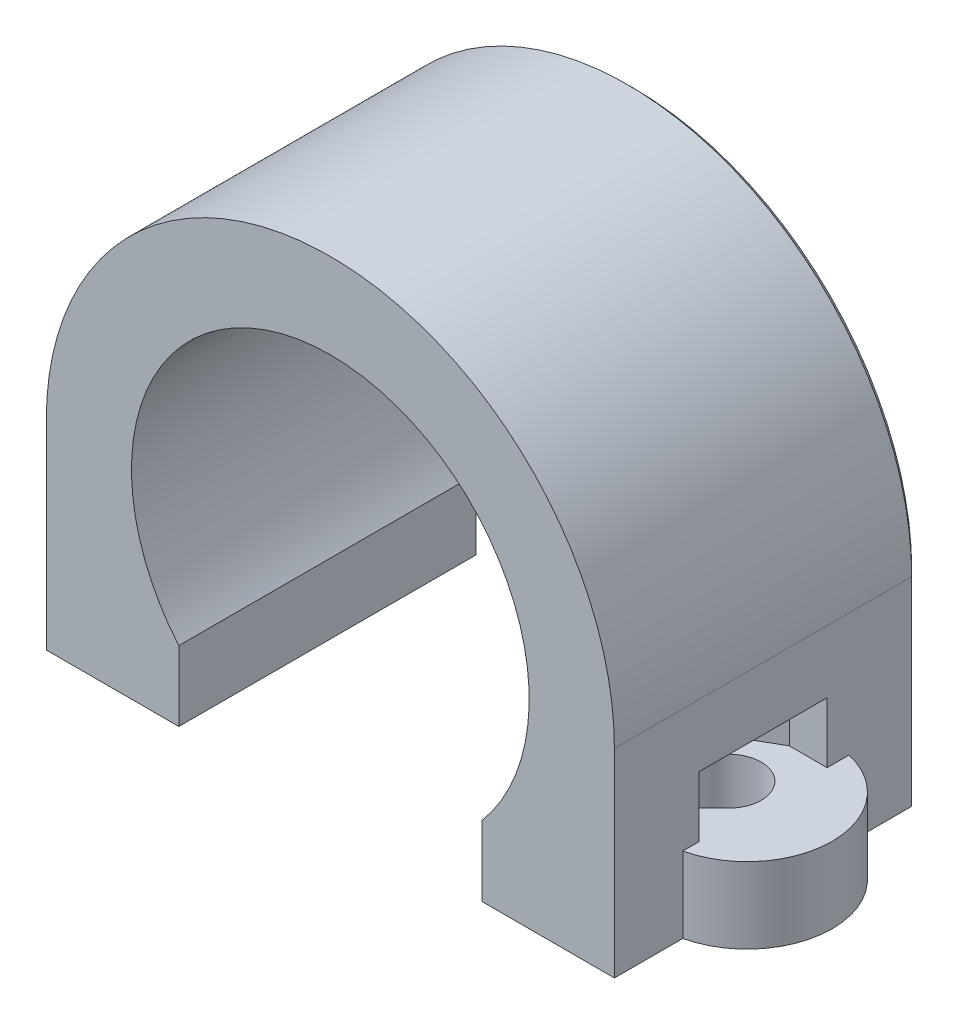
SolidWorks part; units mm, degrees
material "Custom Plastic"
ref_plane "Front Plane" through (0, 0, 0) normal (0, 0, 1) x (1, 0, 0)
ref_plane "Top Plane" through (0, 0, 0) normal (0, 1, 0) x (1, 0, 0)
ref_plane "Right Plane" through (0, 0, 0) normal (1, 0, 0) x (0, 0, -1)
sketch "Sketch1" plane through (0, 0, 0) normal (0, 0, 1) x (1, 0, 0)
  line L0 (-23.622, -10.5) -> (30.4823, -10.5) construction
  line L1 (-23.622, -16.5) -> (30.4823, -16.5) construction
  line L2 (8, -6.8007) -> (8, -10.5)
  line L3 (8, -10.5) -> (15, -10.5)
  line L4 (-15, -10.5) -> (-8, -10.5)
  line L5 (-8, -6.8007) -> (-8, -10.5)
  line L6 (15, 0) -> (15, -10.5)
  line L12 (-15, -10.5) -> (-15, 0)
  arc A4 (8, -6.8007) -> (-8, -6.8007) centre (0, 0) ccw
  arc A5 (15, 0) -> (-15, 0) centre (0, 0) ccw
  dimension "D1" = 16
  dimension "D6" = 21
  dimension "D7" = 4.5
  dimension "D2" = 6
extrude "Boss-Extrude1" add sketch "Sketch1" along normal blind 16
sketch "Sketch4" plane through (0, -10.5, 0) normal (0, -1, 0) x (1, 0, 0)
  line L0 (14, 8) -> (15, 8) construction
  line L1 (15, 16) -> (15, 0) construction
  circle A0 centre (14, 8) radius 4.5
  dimension "D1" = 9
  dimension "D2" = 1
extrude "Boss-Extrude2" add sketch "Sketch4" against normal blind 4
sketch "Sketch2" plane through (0, -10.5, 0) normal (0, -1, 0) x (1, 0, 0)
  line L0 (13, 16) -> (13, 0) construction
  line L3 (14, 8) -> (13, 8) construction
  circle A0 centre (13, 8) radius 1.75
  arc A2 (15, 3.6125) -> (15, 12.3875) centre (14, 8) ccw construction
  dimension "D1" = 3.5
  dimension "D2" = 1
extrude "Cut-Extrude1" cut sketch "Sketch2" against normal blind 10
sketch "Sketch3" plane through (0, -10.5, 0) normal (0, -1, 0) x (1, 0, 0)
  line L0 (10.2, 9.6166) -> (10.2, 9.9166)
  line L1 (13, 11.2332) -> (10.2, 9.6166) construction
  line L2 (10.2, 9.6166) -> (10.2, 6.3834)
  line L3 (10.2, 6.3834) -> (13, 4.7668)
  line L4 (13, 4.7668) -> (15.8, 6.3834) construction
  line L5 (15.8, 6.3834) -> (15.8, 9.6166) construction
  line L6 (15.8, 9.6166) -> (13, 11.2332) construction
  line L7 (13, 11.2332) -> (17.758, 11.2332) construction
  line L8 (10.2, 9.9166) -> (13, 11.5332)
  line L9 (17.758, 11.2332) -> (17.758, 4.7668)
  line L10 (17.758, 4.7668) -> (13, 4.7668)
  line L11 (13, 11.5332) -> (17.758, 11.5332)
  line L12 (17.758, 11.5332) -> (17.758, 11.2332)
  circle A0 centre (13, 8) radius 2.8 construction
  dimension "D1" = 5.6
  dimension "D2" = 0.3
extrude "Cut-Extrude2" cut sketch "Sketch3" against normal blind 3.2 from offset 4 offset against normal yes
mirror "Mirror1" about plane through (0, 0, 0) normal (1, 0, 0) of "Boss-Extrude2", "Cut-Extrude2", "Cut-Extrude1"
chamfer "Chamfer1" distance 0.3 angle 45 8 edges at (-15, -5.25, 0) (-11.5, -10.5, 0) (-8, -8.6504, 0) (0, 10.5, 0) (8, -8.6504, 0) (11.5, -10.5, 0) (15, -5.25, 0) (0, 15, 0)
sketch "Sketch5" plane through (0, -10.5, 0) normal (0, -1, 0) x (1, 0, 0)
  line L0 (-13, 8) -> (-11.7626, 9.2374)
  line L1 (-11.7626, 9.2374) -> (-12.5951, 10.07)
  line L2 (-12.5951, 10.07) -> (-13.4049, 10.07)
  line L3 (-13.4049, 10.07) -> (-14.2374, 9.2374)
  line L4 (-14.2374, 9.2374) -> (-13, 8)
  line L5 (13, 8) -> (14.2374, 9.2374)
  line L6 (14.2374, 9.2374) -> (13.4049, 10.07)
  line L7 (13.4049, 10.07) -> (12.5951, 10.07)
  line L8 (12.5951, 10.07) -> (11.7626, 9.2374)
  line L9 (11.7626, 9.2374) -> (13, 8)
  circle A0 centre (-13, 8) radius 1.75 construction
  circle A1 centre (-13, 8) radius 1.75 construction
  circle A2 centre (13, 8) radius 1.75 construction
  circle A3 centre (13, 8) radius 1.75 construction
  point P0 (-13, 9.75)
  point P11 (13, 9.75)
  dimension "D1" = 0.32
  dimension "D2" = 0.32
extrude "Cut-Extrude3" cut sketch "Sketch5" against normal up to surface (10 mm away) up to face at (-13, -0.5, 6.25)
